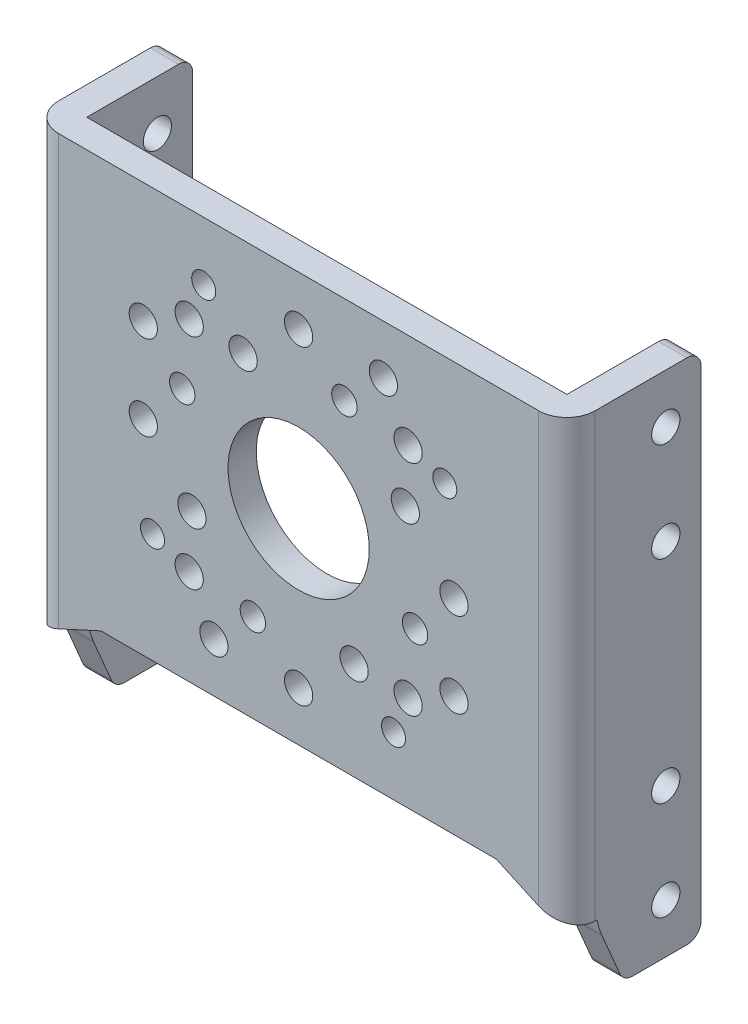
SolidWorks part; units mm, degrees
ref_plane "Front Plane" through (0, 0, 0) normal (0, 0, 1) x (1, 0, 0)
ref_plane "Top Plane" through (0, 0, 0) normal (0, 1, 0) x (1, 0, 0)
ref_plane "Right Plane" through (0, 0, 0) normal (1, 0, 0) x (0, 0, -1)
sketch "Sketch1" plane through (0, 0, 0) normal (0, 0, 1) x (1, 0, 0)
  line L0 (0, 14.5) -> (0, -14.5) construction
  line L1 (-19, 14.5) -> (19, 14.5)
  line L2 (-19, 14.5) -> (-19, -14.5)
  line L3 (-19, -14.5) -> (19, -14.5)
  line L4 (19, 14.5) -> (19, -14.5)
  line L5 (-19, 14.5) -> (19, -14.5) construction
  line L6 (-19, -14.5) -> (19, 14.5) construction
  line L7 (0, 11) -> (19, 11) construction
  line L8 (-8.75, 8.75) -> (8.75, 8.75) construction
  line L9 (-8.75, 8.75) -> (-8.75, -8.75) construction
  line L10 (-8.75, -8.75) -> (8.75, -8.75) construction
  line L11 (8.75, 8.75) -> (8.75, -8.75) construction
  line L12 (-8.75, 8.75) -> (8.75, -8.75) construction
  line L13 (-8.75, -8.75) -> (8.75, 8.75) construction
  line L14 (6, 11) -> (0.8837, 5.8837) construction
  line L15 (3.2423, 8.2423) -> (10.0155, 1.469) construction
  line L16 (7.5556, 3.9289) -> (14.3061, 10.6794) construction
  circle A0 centre (0, 0) radius 5
  circle A1 centre (0, 11) radius 1
  circle A2 centre (7.75, 7.75) radius 1
  circle A3 centre (6, 11) radius 1
  circle A4 centre (3.2423, 8.2423) radius 0.9
  circle A5 centre (7.5556, 3.9289) radius 1
  circle A6 centre (10.3487, 6.722) radius 0.85
  circle A7 centre (3.9289, -7.5556) radius 1
  circle A8 centre (7.75, -7.75) radius 1
  circle A9 centre (6.722, -10.3487) radius 0.85
  circle A10 centre (8.2423, -3.2423) radius 0.9
  circle A11 centre (11, -6) radius 1
  circle A12 centre (11, 0) radius 1
  circle A13 centre (-7.5556, -3.9289) radius 1
  circle A14 centre (-7.75, -7.75) radius 1
  circle A15 centre (-10.3487, -6.722) radius 0.85
  circle A16 centre (-3.2423, -8.2423) radius 0.9
  circle A17 centre (-6, -11) radius 1
  circle A18 centre (0, -11) radius 1
  circle A19 centre (-3.9289, 7.5556) radius 1
  circle A20 centre (-7.75, 7.75) radius 1
  circle A21 centre (-6.722, 10.3487) radius 0.85
  circle A22 centre (-8.2423, 3.2423) radius 0.9
  circle A23 centre (-11, 6) radius 1
  circle A24 centre (-11, 0) radius 1
  point P0 (0, 0)
  point P69 (0, 0)
  dimension "D3" = 11
  dimension "D5" = 2
  dimension "D6" = 6
  dimension "D7" = 1.8
  dimension "D8" = 3.9
  dimension "D9" = 6.1
  dimension "D10" = 3.95
  dimension "D1" = 38
  dimension "D2" = 29
  dimension "D4" = 17.5
  dimension "D11" = 4
extrude "Boss-Extrude1" add sketch "Sketch1" along normal blind 2
sketch "Sketch2" plane through (-19, 0, 0) normal (-1, 0, 0) x (0, 0, 1)
  line L0 (2, 14.5) -> (-7.5, 14.5)
  line L1 (-7.5, 14.5) -> (-7.5, -21.5)
  line L2 (-7.5, -21.5) -> (-2, -21.5)
  line L3 (-2, -21.5) -> (0, -14.5)
  line L4 (0, -14.5) -> (2, -14.5)
  line L5 (2, -14.5) -> (2, 14.5)
  dimension "D1" = 9.5
  dimension "D2" = 36
  dimension "D3" = 5.5
extrude "Boss-Extrude2" add sketch "Sketch2" against normal blind 2
sketch "Sketch3" plane through (0, 0, 2) normal (0, 0, 1) x (1, 0, 0)
  line L0 (-19, -14.5) -> (-14, -14.5)
  line L1 (-19, -14.5) -> (19, -14.5) construction
  line L2 (-14, -14.5) -> (-19, -16.7913)
  line L3 (-19, -21.5) -> (-19, -14.5) construction
  line L4 (-19, -16.7913) -> (-19, -14.5)
  dimension "D1" = 5
  dimension "D2" = 5.5
extrude "Boss-Extrude3" add sketch "Sketch3" against normal blind 2
sketch "Sketch4" plane through (-19, 0, 0) normal (-1, 0, 0) x (0, 0, 1)
  line L0 (0, -14.5) -> (-2, -21.5)
  line L1 (-2, -21.5) -> (0, -16.7913)
  line L2 (0, -16.7913) -> (0, -14.5)
extrude "Boss-Extrude4" add sketch "Sketch4" against normal blind 2
fillet "Fillet4" radius 2 1 edges at (-19, -1.1456, 2)
fillet "Fillet5" radius 6 1 edges at (-18, -16.7913, 0)
fillet "Fillet6" radius 1 3 edges at (-18, 14.5, -7.5) (-18, -21.5, -7.5) (-18, -21.5, -2)
sketch "Sketch5" plane through (-19, 0, 0) normal (-1, 0, 0) x (0, 0, 1)
  line L0 (-5, 14.5) -> (-5, -21.5) construction
  line L1 (0, 14.5) -> (-6.5, 14.5) construction
  line L2 (-6.5, -21.5) -> (-2.6617, -21.5) construction
  line L3 (-7.5, 13.5) -> (-7.5, -20.5) construction
  line L4 (-7.5, -3.5) -> (-5, -3.5) construction
  circle A0 centre (-5, 11) radius 1
  circle A1 centre (-5, -18) radius 1
  circle A2 centre (-5, 4) radius 1
  circle A3 centre (-5, -11) radius 1
  dimension "D2" = 14.5
  dimension "D4" = 7.5
  dimension "D1" = 2.5
  dimension "D3" = 14.5
  dimension "D5" = 7.5
extrude "Cut-Extrude1" cut sketch "Sketch5" against normal blind 2
mirror "Mirror3" about plane through (0, 0, 0) normal (1, 0, 0) of "Cut-Extrude1", "Fillet6", "Boss-Extrude4", "Boss-Extrude2", "Boss-Extrude3", "Fillet5"
fillet "Fillet7" radius 2 1 edges at (19, -1.1456, 2)
